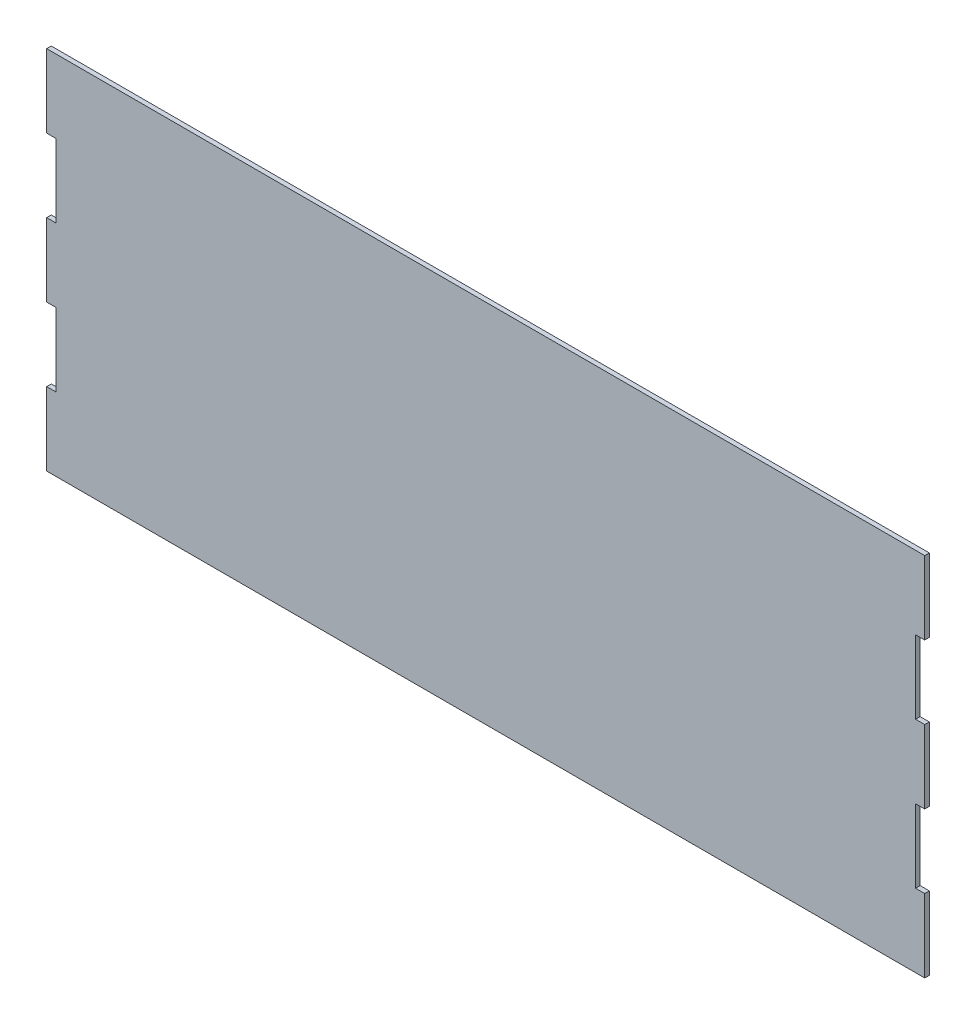
SolidWorks part; units mm, degrees
ref_plane "Front Plane" through (0, 0, 0) normal (0, 0, 1) x (1, 0, 0)
ref_plane "Top Plane" through (0, 0, 0) normal (0, 1, 0) x (1, 0, 0)
ref_plane "Right Plane" through (0, 0, 0) normal (1, 0, 0) x (0, 0, -1)
sketch "Sketch1" plane through (0, 0, 0) normal (0, 0, 1) x (1, 0, 0)
  line L0 (0, 203.2) -> (6.35, 203.2)
  line L1 (0, 0) -> (609.6, 0)
  line L2 (0, 0) -> (0, 50.8)
  line L3 (0, 254) -> (609.6, 254)
  line L4 (609.6, 0) -> (609.6, 50.8)
  line L5 (6.35, 203.2) -> (6.35, 152.4)
  line L6 (6.35, 152.4) -> (0, 152.4)
  line L7 (0, 101.6) -> (6.35, 101.6)
  line L8 (6.35, 101.6) -> (6.35, 50.8)
  line L9 (6.35, 50.8) -> (0, 50.8)
  line L10 (0, 0) -> (6.35, 0)
  line L11 (6.35, 0) -> (6.35, -50.8)
  line L12 (6.35, -50.8) -> (0, -50.8)
  line L13 (0, 101.6) -> (0, 152.4)
  line L14 (0, 203.2) -> (0, 254)
  line L15 (304.8, 254) -> (304.8, 0) construction
  line L16 (603.25, 50.8) -> (609.6, 50.8)
  line L17 (603.25, 101.6) -> (603.25, 50.8)
  line L18 (609.6, 101.6) -> (603.25, 101.6)
  line L19 (603.25, 152.4) -> (609.6, 152.4)
  line L20 (603.25, 203.2) -> (603.25, 152.4)
  line L21 (609.6, 203.2) -> (603.25, 203.2)
  line L22 (609.6, 203.2) -> (609.6, 254)
  line L23 (609.6, 101.6) -> (609.6, 152.4)
  line L24 (25.4, 254) -> (25.4, 0) construction
  line L25 (584.2, 254) -> (584.2, 0) construction
  dimension "D1" = 254
  dimension "D2" = 609.6
  dimension "D3" = 6.35
  dimension "D4" = 50.8
  dimension "D5" = 50.8
  dimension "D7" = 25.4
  dimension "D8" = 25.4
  dimension "D6" = 3
extrude "Boss-Extrude1" add sketch "Sketch1" along normal blind 3.175 contours L18 L23 L19 L20 L21 L22 L3 L14 L0 L5 L6 L13 L7 L8 L9 L2 L1 L4 L16 L17 region at (304.8, 127, 0)
sketch "Sketch4" plane through (0, 0, 3.175) normal (0, 0, 1) x (1, 0, 0)
  line L0 (327.574, 254) -> (327.574, 0) construction
  line L1 (331.2055, -0.0167) -> (331.2055, 59.8139)
  line L2 (331.2055, 74.3399) -> (331.2055, 179.5864)
  line L3 (331.2055, 194.1124) -> (331.2055, 254)
  line L4 (327.574, 134.2248) -> (327.574, 239.474)
  line L5 (327.574, 14.4495) -> (327.574, 119.6988)
  line L6 (584.2, 194.1124) -> (584.2, 254)
  line L7 (84.2635, -0.0167) -> (77.0005, -0.0167)
  line L8 (331.2055, -0.0167) -> (338.4685, -0.0167)
  line L9 (331.2055, 254) -> (338.4685, 254)
  line L10 (77.0005, -0.0167) -> (64.8955, -0.0167)
  line L11 (84.2635, 254) -> (77.0005, 254)
  line L12 (77.0005, 254) -> (64.8955, 254)
  line L13 (87.895, 134.2248) -> (87.895, 239.474)
  line L14 (73.369, 134.2248) -> (73.369, 239.474)
  line L15 (80.632, 134.2248) -> (80.632, 239.474)
  line L16 (77.0005, 74.3399) -> (77.0005, 179.5864)
  line L17 (80.632, 14.4495) -> (80.632, 119.6988)
  line L18 (84.2635, 194.1124) -> (84.2635, 254)
  line L19 (87.895, 14.4495) -> (87.895, 119.6988)
  line L20 (77.0005, 194.1124) -> (77.0005, 254)
  line L21 (73.369, 14.4495) -> (73.369, 119.6988)
  line L22 (84.2635, 74.3399) -> (84.2635, 179.5864)
  line L23 (84.2635, -0.0167) -> (84.2635, 59.8139)
  line L24 (77.0005, -0.0167) -> (77.0005, 59.8139)
  line L25 (91.5265, -0.0167) -> (84.2635, -0.0167)
  line L26 (98.7895, 254) -> (91.5265, 254)
  line L27 (91.5265, 254) -> (84.2635, 254)
  line L28 (98.7895, -0.0167) -> (91.5265, -0.0167)
  line L29 (113.3155, 254) -> (106.0525, 254)
  line L30 (106.0525, 254) -> (98.7895, 254)
  line L31 (113.3155, -0.0167) -> (106.0525, -0.0167)
  line L32 (106.0525, -0.0167) -> (98.7895, -0.0167)
  line L33 (95.158, 134.2248) -> (95.158, 239.474)
  line L34 (109.684, 14.4495) -> (109.684, 119.6988)
  line L35 (113.3155, 194.1124) -> (113.3155, 254)
  line L36 (116.947, 134.2248) -> (116.947, 239.474)
  line L37 (91.5265, -0.0167) -> (91.5265, 59.8139)
  line L38 (98.7895, 194.1124) -> (98.7895, 254)
  line L39 (91.5265, 74.3399) -> (91.5265, 179.5864)
  line L40 (109.684, 134.2248) -> (109.684, 239.474)
  line L41 (113.3155, 74.3399) -> (113.3155, 179.5864)
  line L42 (98.7895, 74.3399) -> (98.7895, 179.5864)
  line L43 (106.0525, 74.3399) -> (106.0525, 179.5864)
  line L44 (116.947, 14.4495) -> (116.947, 119.6988)
  line L45 (102.421, 134.2248) -> (102.421, 239.474)
  line L46 (91.5265, 194.1124) -> (91.5265, 254)
  line L47 (95.158, 14.4495) -> (95.158, 119.6988)
  line L48 (98.7895, -0.0167) -> (98.7895, 59.8139)
  line L49 (102.421, 14.4495) -> (102.421, 119.6988)
  line L50 (106.0525, 194.1124) -> (106.0525, 254)
  line L51 (113.3155, -0.0167) -> (113.3155, 59.8139)
  line L52 (106.0525, -0.0167) -> (106.0525, 59.8139)
  line L53 (120.5785, 254) -> (113.3155, 254)
  line L54 (127.8415, -0.0167) -> (120.5785, -0.0167)
  line L55 (120.5785, -0.0167) -> (113.3155, -0.0167)
  line L56 (127.8415, 254) -> (120.5785, 254)
  line L57 (142.3675, -0.0167) -> (135.1045, -0.0167)
  line L58 (135.1045, -0.0167) -> (127.8415, -0.0167)
  line L59 (142.3675, 254) -> (135.1045, 254)
  line L60 (135.1045, 254) -> (127.8415, 254)
  line L61 (138.736, 134.2248) -> (138.736, 239.474)
  line L62 (120.5785, -0.0167) -> (120.5785, 59.8139)
  line L63 (120.5785, 194.1124) -> (120.5785, 254)
  line L64 (127.8415, -0.0167) -> (127.8415, 59.8139)
  line L65 (124.21, 14.4495) -> (124.21, 119.6988)
  line L66 (127.8415, 194.1124) -> (127.8415, 254)
  line L67 (142.3675, 194.1124) -> (142.3675, 254)
  line L68 (120.5785, 74.3399) -> (120.5785, 179.5864)
  line L69 (142.3675, 74.3399) -> (142.3675, 179.5864)
  line L70 (145.999, 14.4495) -> (145.999, 119.6988)
  line L71 (127.8415, 74.3399) -> (127.8415, 179.5864)
  line L72 (145.999, 134.2248) -> (145.999, 239.474)
  line L73 (131.473, 134.2248) -> (131.473, 239.474)
  line L74 (131.473, 14.4495) -> (131.473, 119.6988)
  line L75 (135.1045, 74.3399) -> (135.1045, 179.5864)
  line L76 (135.1045, 194.1124) -> (135.1045, 254)
  line L77 (124.21, 134.2248) -> (124.21, 239.474)
  line L78 (138.736, 14.4495) -> (138.736, 119.6988)
  line L80 (142.3675, -0.0167) -> (142.3675, 59.8139)
  line L81 (135.1045, -0.0167) -> (135.1045, 59.8139)
  line L83 (149.6305, -0.0167) -> (142.3675, -0.0167)
  line L85 (156.8935, -0.0167) -> (149.6305, -0.0167)
  line L86 (156.8935, 254) -> (149.6305, 254)
  line L87 (149.6305, 254) -> (142.3675, 254)
  line L88 (171.4195, -0.0167) -> (164.1565, -0.0167)
  line L89 (164.1565, -0.0167) -> (156.8935, -0.0167)
  line L90 (171.4195, 254) -> (164.1565, 254)
  line L91 (164.1565, 254) -> (156.8935, 254)
  line L92 (175.051, 134.2248) -> (175.051, 239.474)
  line L93 (156.8935, 194.1124) -> (156.8935, 254)
  line L94 (153.262, 134.2248) -> (153.262, 239.474)
  line L95 (149.6305, 194.1124) -> (149.6305, 254)
  line L96 (149.6305, -0.0167) -> (149.6305, 59.8139)
  line L97 (156.8935, 74.3399) -> (156.8935, 179.5864)
  line L98 (149.6305, 74.3399) -> (149.6305, 179.5864)
  line L99 (175.051, 14.4495) -> (175.051, 119.6988)
  line L100 (167.788, 134.2248) -> (167.788, 239.474)
  line L101 (160.525, 134.2248) -> (160.525, 239.474)
  line L102 (171.4195, 74.3399) -> (171.4195, 179.5864)
  line L103 (171.4195, 194.1124) -> (171.4195, 254)
  line L104 (167.788, 14.4495) -> (167.788, 119.6988)
  line L105 (156.8935, -0.0167) -> (156.8935, 59.8139)
  line L106 (164.1565, 74.3399) -> (164.1565, 179.5864)
  line L107 (164.1565, 194.1124) -> (164.1565, 254)
  line L108 (153.262, 14.4495) -> (153.262, 119.6988)
  line L109 (160.525, 14.4495) -> (160.525, 119.6988)
  line L110 (171.4195, -0.0167) -> (171.4195, 59.8139)
  line L111 (164.1565, -0.0167) -> (164.1565, 59.8139)
  line L112 (178.6825, -0.0167) -> (171.4195, -0.0167)
  line L113 (193.2085, 254) -> (185.9455, 254)
  line L114 (185.9455, -0.0167) -> (178.6825, -0.0167)
  line L115 (200.4715, 254) -> (193.2085, 254)
  line L116 (185.9455, 254) -> (178.6825, 254)
  line L117 (178.6825, 254) -> (171.4195, 254)
  line L118 (200.4715, -0.0167) -> (193.2085, -0.0167)
  line L119 (193.2085, -0.0167) -> (185.9455, -0.0167)
  line L120 (182.314, 14.4495) -> (182.314, 119.6988)
  line L121 (185.9455, 74.3399) -> (185.9455, 179.5864)
  line L122 (189.577, 14.4495) -> (189.577, 119.6988)
  line L123 (178.6825, 74.3399) -> (178.6825, 179.5864)
  line L124 (204.103, 134.2248) -> (204.103, 239.474)
  line L125 (193.2085, 194.1124) -> (193.2085, 254)
  line L126 (193.2085, 74.3399) -> (193.2085, 179.5864)
  line L127 (204.103, 14.4495) -> (204.103, 119.6988)
  line L128 (196.84, 134.2248) -> (196.84, 239.474)
  line L129 (189.577, 134.2248) -> (189.577, 239.474)
  line L130 (200.4715, 194.1124) -> (200.4715, 254)
  line L131 (178.6825, -0.0167) -> (178.6825, 59.8139)
  line L132 (185.9455, 194.1124) -> (185.9455, 254)
  line L133 (200.4715, 74.3399) -> (200.4715, 179.5864)
  line L134 (196.84, 14.4495) -> (196.84, 119.6988)
  line L135 (178.6825, 194.1124) -> (178.6825, 254)
  line L136 (182.314, 134.2248) -> (182.314, 239.474)
  line L137 (185.9455, -0.0167) -> (185.9455, 59.8139)
  line L138 (200.4715, -0.0167) -> (200.4715, 59.8139)
  line L139 (193.2085, -0.0167) -> (193.2085, 59.8139)
  line L140 (207.7345, 254) -> (200.4715, 254)
  line L141 (222.2605, 254) -> (214.9975, 254)
  line L142 (214.9975, 254) -> (207.7345, 254)
  line L143 (214.9975, -0.0167) -> (207.7345, -0.0167)
  line L144 (207.7345, -0.0167) -> (200.4715, -0.0167)
  line L145 (229.5235, 254) -> (222.2605, 254)
  line L146 (229.5235, -0.0167) -> (222.2605, -0.0167)
  line L147 (222.2605, -0.0167) -> (214.9975, -0.0167)
  line L148 (214.9975, -0.0167) -> (214.9975, 59.8139)
  line L149 (229.5235, 74.3399) -> (229.5235, 179.5864)
  line L150 (214.9975, 74.3399) -> (214.9975, 179.5864)
  line L151 (222.2605, 194.1124) -> (222.2605, 254)
  line L152 (218.629, 134.2248) -> (218.629, 239.474)
  line L153 (222.2605, 74.3399) -> (222.2605, 179.5864)
  line L154 (211.366, 134.2248) -> (211.366, 239.474)
  line L155 (207.7345, -0.0167) -> (207.7345, 59.8139)
  line L156 (218.629, 14.4495) -> (218.629, 119.6988)
  line L157 (225.892, 14.4495) -> (225.892, 119.6988)
  line L158 (207.7345, 194.1124) -> (207.7345, 254)
  line L159 (233.155, 14.4495) -> (233.155, 119.6988)
  line L160 (214.9975, 194.1124) -> (214.9975, 254)
  line L161 (207.7345, 74.3399) -> (207.7345, 179.5864)
  line L162 (211.366, 14.4495) -> (211.366, 119.6988)
  line L163 (229.5235, 194.1124) -> (229.5235, 254)
  line L164 (233.155, 134.2248) -> (233.155, 239.474)
  line L165 (225.892, 134.2248) -> (225.892, 239.474)
  line L166 (229.5235, -0.0167) -> (229.5235, 59.8139)
  line L167 (222.2605, -0.0167) -> (222.2605, 59.8139)
  line L168 (244.0495, 254) -> (236.7865, 254)
  line L169 (236.7865, 254) -> (229.5235, 254)
  line L170 (244.0495, -0.0167) -> (236.7865, -0.0167)
  line L171 (236.7865, -0.0167) -> (229.5235, -0.0167)
  line L172 (251.3125, 254) -> (244.0495, 254)
  line L173 (258.5755, -0.0167) -> (251.3125, -0.0167)
  line L174 (251.3125, -0.0167) -> (244.0495, -0.0167)
  line L175 (258.5755, 254) -> (251.3125, 254)
  line L176 (244.0495, 194.1124) -> (244.0495, 254)
  line L177 (236.7865, 194.1124) -> (236.7865, 254)
  line L178 (236.7865, 74.3399) -> (236.7865, 179.5864)
  line L179 (247.681, 134.2248) -> (247.681, 239.474)
  line L180 (254.944, 134.2248) -> (254.944, 239.474)
  line L181 (258.5755, 74.3399) -> (258.5755, 179.5864)
  line L182 (244.0495, 74.3399) -> (244.0495, 179.5864)
  line L183 (251.3125, 194.1124) -> (251.3125, 254)
  line L184 (262.207, 134.2248) -> (262.207, 239.474)
  line L185 (244.0495, -0.0167) -> (244.0495, 59.8139)
  line L186 (258.5755, 194.1124) -> (258.5755, 254)
  line L187 (247.681, 14.4495) -> (247.681, 119.6988)
  line L188 (240.418, 134.2248) -> (240.418, 239.474)
  line L189 (254.944, 14.4495) -> (254.944, 119.6988)
  line L190 (262.207, 14.4495) -> (262.207, 119.6988)
  line L191 (251.3125, 74.3399) -> (251.3125, 179.5864)
  line L192 (236.7865, -0.0167) -> (236.7865, 59.8139)
  line L193 (240.418, 14.4495) -> (240.418, 119.6988)
  line L194 (258.5755, -0.0167) -> (258.5755, 59.8139)
  line L195 (251.3125, -0.0167) -> (251.3125, 59.8139)
  line L196 (280.3645, 254) -> (273.1015, 254)
  line L197 (273.1015, -0.0167) -> (265.8385, -0.0167)
  line L198 (265.8385, -0.0167) -> (258.5755, -0.0167)
  line L199 (287.6275, 254) -> (280.3645, 254)
  line L200 (273.1015, 254) -> (265.8385, 254)
  line L201 (265.8385, 254) -> (258.5755, 254)
  line L202 (287.6275, -0.0167) -> (280.3645, -0.0167)
  line L203 (280.3645, -0.0167) -> (273.1015, -0.0167)
  line L204 (283.996, 134.2248) -> (283.996, 239.474)
  line L205 (291.259, 134.2248) -> (291.259, 239.474)
  line L206 (280.3645, 194.1124) -> (280.3645, 254)
  line L207 (269.47, 134.2248) -> (269.47, 239.474)
  line L208 (273.1015, 74.3399) -> (273.1015, 179.5864)
  line L209 (276.733, 134.2248) -> (276.733, 239.474)
  line L210 (287.6275, 74.3399) -> (287.6275, 179.5864)
  line L211 (291.259, 14.4495) -> (291.259, 119.6988)
  line L212 (287.6275, 194.1124) -> (287.6275, 254)
  line L213 (276.733, 14.4495) -> (276.733, 119.6988)
  line L214 (273.1015, 194.1124) -> (273.1015, 254)
  line L215 (269.47, 14.4495) -> (269.47, 119.6988)
  line L216 (273.1015, -0.0167) -> (273.1015, 59.8139)
  line L217 (265.8385, -0.0167) -> (265.8385, 59.8139)
  line L218 (283.996, 14.4495) -> (283.996, 119.6988)
  line L219 (280.3645, 74.3399) -> (280.3645, 179.5864)
  line L220 (265.8385, 74.3399) -> (265.8385, 179.5864)
  line L221 (265.8385, 194.1124) -> (265.8385, 254)
  line L222 (287.6275, -0.0167) -> (287.6275, 59.8139)
  line L223 (280.3645, -0.0167) -> (280.3645, 59.8139)
  line L224 (294.8905, 254) -> (287.6275, 254)
  line L225 (294.8905, -0.0167) -> (287.6275, -0.0167)
  line L226 (298.522, 14.4495) -> (298.522, 119.6988)
  line L227 (294.8905, 74.3399) -> (294.8905, 179.5864)
  line L228 (294.8905, -0.0167) -> (294.8905, 59.8139)
  line L229 (294.8905, 194.1124) -> (294.8905, 254)
  line L230 (298.522, 134.2248) -> (298.522, 239.474)
  line L231 (302.1535, 254) -> (294.8905, 254)
  line L232 (302.1535, -0.0167) -> (294.8905, -0.0167)
  line L233 (302.1535, -0.0167) -> (302.1535, 59.8139)
  line L234 (302.1535, 194.1124) -> (302.1535, 254)
  line L235 (305.785, 14.4495) -> (305.785, 119.6988)
  line L236 (302.1535, 74.3399) -> (302.1535, 179.5864)
  line L237 (305.785, 134.2248) -> (305.785, 239.474)
  line L238 (309.4165, 254) -> (302.1535, 254)
  line L239 (309.4165, -0.0167) -> (302.1535, -0.0167)
  line L240 (313.048, 14.4495) -> (313.048, 119.6988)
  line L241 (309.4165, 74.3399) -> (309.4165, 179.5864)
  line L242 (313.048, 134.2248) -> (313.048, 239.474)
  line L243 (309.4165, 194.1124) -> (309.4165, 254)
  line L244 (309.4165, -0.0167) -> (309.4165, 59.8139)
  line L245 (316.6795, 254) -> (309.4165, 254)
  line L246 (316.6795, -0.0167) -> (309.4165, -0.0167)
  line L247 (320.311, 14.4495) -> (320.311, 119.6988)
  line L248 (320.311, 134.2248) -> (320.311, 239.474)
  line L249 (316.6795, 194.1124) -> (316.6795, 254)
  line L250 (316.6795, 74.3399) -> (316.6795, 179.5864)
  line L251 (316.6795, -0.0167) -> (316.6795, 59.8139)
  line L252 (70.948, -0.0167) -> (70.948, 59.8139)
  line L253 (70.948, 74.3399) -> (70.948, 179.5864)
  line L254 (323.9425, 254) -> (316.6795, 254)
  line L255 (323.9425, -0.0167) -> (316.6795, -0.0167)
  line L256 (70.948, 194.1124) -> (70.948, 254)
  line L257 (323.9425, 194.1124) -> (323.9425, 254)
  line L258 (323.9425, 74.3399) -> (323.9425, 179.5864)
  line L259 (323.9425, -0.0167) -> (323.9425, 59.8139)
  line L260 (70.948, 260.5884) -> (70.948, -3.5124) construction
  line L261 (25.4, 254) -> (25.4, 0) construction
  line L262 (0, 0) -> (0, 50.8) construction
  line L263 (43.1065, 254) -> (50.3695, 254)
  line L264 (43.1065, -0.0167) -> (50.3695, -0.0167)
  line L265 (35.8435, -0.0167) -> (35.8435, 59.8139)
  line L266 (28.5805, -0.0167) -> (28.5805, 59.8139)
  line L267 (35.8435, 194.1124) -> (35.8435, 254)
  line L268 (39.475, 14.4495) -> (39.475, 119.6988)
  line L269 (43.1065, -0.0167) -> (43.1065, 59.8139)
  line L270 (39.475, 134.2248) -> (39.475, 239.474)
  line L271 (24.949, 14.4495) -> (24.949, 119.6988)
  line L272 (35.8435, 74.3399) -> (35.8435, 179.5864)
  line L273 (43.1065, 74.3399) -> (43.1065, 179.5864)
  line L274 (28.5805, 74.3399) -> (28.5805, 179.5864)
  line L275 (32.212, 134.2248) -> (32.212, 239.474)
  line L276 (43.1065, 194.1124) -> (43.1065, 254)
  line L277 (24.949, 134.2248) -> (24.949, 239.474)
  line L278 (28.5805, 194.1124) -> (28.5805, 254)
  line L279 (32.212, 14.4495) -> (32.212, 119.6988)
  line L280 (35.8435, -0.0167) -> (43.1065, -0.0167)
  line L281 (28.5805, -0.0167) -> (35.8435, -0.0167)
  line L282 (35.8435, 254) -> (43.1065, 254)
  line L283 (28.5805, 254) -> (35.8435, 254)
  line L284 (46.738, 14.4495) -> (46.738, 119.6988)
  line L285 (50.3695, 194.1124) -> (50.3695, 254)
  line L286 (50.3695, 74.3399) -> (50.3695, 179.5864)
  line L287 (50.3695, -0.0167) -> (50.3695, 59.8139)
  line L288 (46.738, 134.2248) -> (46.738, 239.474)
  line L289 (50.3695, 254) -> (57.6325, 254)
  line L290 (50.3695, -0.0167) -> (57.6325, -0.0167)
  line L291 (64.8955, -0.0167) -> (64.8955, 59.8139)
  line L292 (57.6325, -0.0167) -> (57.6325, 59.8139)
  line L293 (57.6325, 74.3399) -> (57.6325, 179.5864)
  line L294 (68.527, 14.4495) -> (68.527, 119.6988)
  line L295 (64.8955, 194.1124) -> (64.8955, 254)
  line L296 (54.001, 14.4495) -> (54.001, 119.6988)
  line L297 (57.6325, 194.1124) -> (57.6325, 254)
  line L298 (61.264, 14.4495) -> (61.264, 119.6988)
  line L299 (64.8955, 74.3399) -> (64.8955, 179.5864)
  line L300 (61.264, 134.2248) -> (61.264, 239.474)
  line L301 (68.527, 134.2248) -> (68.527, 239.474)
  line L302 (54.001, 134.2248) -> (54.001, 239.474)
  line L303 (57.6325, 254) -> (64.8955, 254)
  line L304 (57.6325, -0.0167) -> (64.8955, -0.0167)
  line L541 (584.2, 74.3399) -> (584.2, 179.5864)
  line L542 (584.2, -0.0167) -> (584.2, 59.8139)
  line L543 (338.4685, -0.0167) -> (338.4685, 59.8139)
  line L544 (338.4685, 74.3399) -> (338.4685, 179.5864)
  line L545 (338.4685, 194.1124) -> (338.4685, 254)
  line L546 (334.837, 134.2248) -> (334.837, 239.474)
  line L547 (334.837, 14.4495) -> (334.837, 119.6988)
  line L548 (338.4685, -0.0167) -> (345.7315, -0.0167)
  line L549 (338.4685, 254) -> (345.7315, 254)
  line L550 (345.7315, -0.0167) -> (345.7315, 59.8139)
  line L551 (345.7315, 194.1124) -> (345.7315, 254)
  line L552 (342.1, 134.2248) -> (342.1, 239.474)
  line L553 (345.7315, 74.3399) -> (345.7315, 179.5864)
  line L554 (342.1, 14.4495) -> (342.1, 119.6988)
  line L555 (345.7315, -0.0167) -> (352.9945, -0.0167)
  line L556 (345.7315, 254) -> (352.9945, 254)
  line L557 (349.363, 134.2248) -> (349.363, 239.474)
  line L558 (352.9945, 74.3399) -> (352.9945, 179.5864)
  line L559 (349.363, 14.4495) -> (349.363, 119.6988)
  line L560 (352.9945, 194.1124) -> (352.9945, 254)
  line L561 (352.9945, -0.0167) -> (352.9945, 59.8139)
  line L562 (352.9945, -0.0167) -> (360.2575, -0.0167)
  line L563 (352.9945, 254) -> (360.2575, 254)
  line L564 (356.626, 134.2248) -> (356.626, 239.474)
  line L565 (360.2575, 194.1124) -> (360.2575, 254)
  line L566 (360.2575, -0.0167) -> (360.2575, 59.8139)
  line L567 (360.2575, 74.3399) -> (360.2575, 179.5864)
  line L568 (356.626, 14.4495) -> (356.626, 119.6988)
  line L569 (360.2575, -0.0167) -> (367.5205, -0.0167)
  line L570 (360.2575, 254) -> (367.5205, 254)
  line L571 (374.7835, -0.0167) -> (374.7835, 59.8139)
  line L572 (367.5205, -0.0167) -> (367.5205, 59.8139)
  line L573 (389.3095, 194.1124) -> (389.3095, 254)
  line L574 (389.3095, 74.3399) -> (389.3095, 179.5864)
  line L575 (374.7835, 74.3399) -> (374.7835, 179.5864)
  line L576 (371.152, 14.4495) -> (371.152, 119.6988)
  line L577 (389.3095, -0.0167) -> (389.3095, 59.8139)
  line L578 (382.0465, -0.0167) -> (382.0465, 59.8139)
  line L579 (385.678, 14.4495) -> (385.678, 119.6988)
  line L580 (382.0465, 194.1124) -> (382.0465, 254)
  line L581 (378.415, 14.4495) -> (378.415, 119.6988)
  line L582 (367.5205, 194.1124) -> (367.5205, 254)
  line L583 (363.889, 14.4495) -> (363.889, 119.6988)
  line L584 (367.5205, 74.3399) -> (367.5205, 179.5864)
  line L585 (378.415, 134.2248) -> (378.415, 239.474)
  line L586 (382.0465, 74.3399) -> (382.0465, 179.5864)
  line L587 (385.678, 134.2248) -> (385.678, 239.474)
  line L588 (374.7835, 194.1124) -> (374.7835, 254)
  line L589 (363.889, 134.2248) -> (363.889, 239.474)
  line L590 (371.152, 134.2248) -> (371.152, 239.474)
  line L591 (374.7835, -0.0167) -> (382.0465, -0.0167)
  line L592 (367.5205, -0.0167) -> (374.7835, -0.0167)
  line L593 (389.3095, 254) -> (396.5725, 254)
  line L594 (382.0465, 254) -> (389.3095, 254)
  line L595 (367.5205, 254) -> (374.7835, 254)
  line L596 (389.3095, -0.0167) -> (396.5725, -0.0167)
  line L597 (382.0465, -0.0167) -> (389.3095, -0.0167)
  line L598 (374.7835, 254) -> (382.0465, 254)
  line L599 (403.8355, -0.0167) -> (403.8355, 59.8139)
  line L600 (396.5725, -0.0167) -> (396.5725, 59.8139)
  line L601 (414.73, 14.4495) -> (414.73, 119.6988)
  line L602 (418.3615, -0.0167) -> (418.3615, 59.8139)
  line L603 (403.8355, 74.3399) -> (403.8355, 179.5864)
  line L604 (392.941, 14.4495) -> (392.941, 119.6988)
  line L605 (400.204, 14.4495) -> (400.204, 119.6988)
  line L606 (414.73, 134.2248) -> (414.73, 239.474)
  line L607 (407.467, 14.4495) -> (407.467, 119.6988)
  line L608 (396.5725, 194.1124) -> (396.5725, 254)
  line L609 (411.0985, -0.0167) -> (411.0985, 59.8139)
  line L610 (392.941, 134.2248) -> (392.941, 239.474)
  line L611 (403.8355, 194.1124) -> (403.8355, 254)
  line L612 (411.0985, 74.3399) -> (411.0985, 179.5864)
  line L613 (396.5725, 74.3399) -> (396.5725, 179.5864)
  line L614 (400.204, 134.2248) -> (400.204, 239.474)
  line L615 (407.467, 134.2248) -> (407.467, 239.474)
  line L616 (418.3615, 74.3399) -> (418.3615, 179.5864)
  line L617 (418.3615, 194.1124) -> (418.3615, 254)
  line L618 (411.0985, 194.1124) -> (411.0985, 254)
  line L619 (396.5725, 254) -> (403.8355, 254)
  line L620 (403.8355, -0.0167) -> (411.0985, -0.0167)
  line L621 (396.5725, -0.0167) -> (403.8355, -0.0167)
  line L622 (403.8355, 254) -> (411.0985, 254)
  line L623 (418.3615, -0.0167) -> (425.6245, -0.0167)
  line L624 (411.0985, -0.0167) -> (418.3615, -0.0167)
  line L625 (418.3615, 254) -> (425.6245, 254)
  line L626 (411.0985, 254) -> (418.3615, 254)
  line L627 (432.8875, -0.0167) -> (432.8875, 59.8139)
  line L628 (425.6245, -0.0167) -> (425.6245, 59.8139)
  line L629 (429.256, 134.2248) -> (429.256, 239.474)
  line L630 (421.993, 134.2248) -> (421.993, 239.474)
  line L631 (425.6245, 194.1124) -> (425.6245, 254)
  line L632 (443.782, 14.4495) -> (443.782, 119.6988)
  line L633 (447.4135, 74.3399) -> (447.4135, 179.5864)
  line L634 (440.1505, 194.1124) -> (440.1505, 254)
  line L635 (421.993, 14.4495) -> (421.993, 119.6988)
  line L636 (447.4135, 194.1124) -> (447.4135, 254)
  line L637 (429.256, 14.4495) -> (429.256, 119.6988)
  line L638 (436.519, 14.4495) -> (436.519, 119.6988)
  line L639 (447.4135, -0.0167) -> (447.4135, 59.8139)
  line L640 (443.782, 134.2248) -> (443.782, 239.474)
  line L641 (432.8875, 74.3399) -> (432.8875, 179.5864)
  line L642 (436.519, 134.2248) -> (436.519, 239.474)
  line L643 (432.8875, 194.1124) -> (432.8875, 254)
  line L644 (440.1505, 74.3399) -> (440.1505, 179.5864)
  line L645 (425.6245, 74.3399) -> (425.6245, 179.5864)
  line L646 (440.1505, -0.0167) -> (440.1505, 59.8139)
  line L647 (432.8875, -0.0167) -> (440.1505, -0.0167)
  line L648 (425.6245, -0.0167) -> (432.8875, -0.0167)
  line L649 (425.6245, 254) -> (432.8875, 254)
  line L650 (447.4135, -0.0167) -> (454.6765, -0.0167)
  line L651 (440.1505, -0.0167) -> (447.4135, -0.0167)
  line L652 (440.1505, 254) -> (447.4135, 254)
  line L653 (432.8875, 254) -> (440.1505, 254)
  line L654 (447.4135, 254) -> (454.6765, 254)
  line L655 (461.9395, -0.0167) -> (461.9395, 59.8139)
  line L656 (454.6765, -0.0167) -> (454.6765, 59.8139)
  line L657 (469.2025, -0.0167) -> (469.2025, 59.8139)
  line L658 (472.834, 134.2248) -> (472.834, 239.474)
  line L659 (476.4655, 194.1124) -> (476.4655, 254)
  line L660 (458.308, 14.4495) -> (458.308, 119.6988)
  line L661 (454.6765, 74.3399) -> (454.6765, 179.5864)
  line L662 (469.2025, 194.1124) -> (469.2025, 254)
  line L663 (476.4655, -0.0167) -> (476.4655, 59.8139)
  line L664 (454.6765, 194.1124) -> (454.6765, 254)
  line L665 (465.571, 134.2248) -> (465.571, 239.474)
  line L666 (458.308, 134.2248) -> (458.308, 239.474)
  line L667 (451.045, 14.4495) -> (451.045, 119.6988)
  line L668 (461.9395, 74.3399) -> (461.9395, 179.5864)
  line L669 (461.9395, 194.1124) -> (461.9395, 254)
  line L670 (451.045, 134.2248) -> (451.045, 239.474)
  line L671 (476.4655, 74.3399) -> (476.4655, 179.5864)
  line L672 (465.571, 14.4495) -> (465.571, 119.6988)
  line L673 (469.2025, 74.3399) -> (469.2025, 179.5864)
  line L674 (472.834, 14.4495) -> (472.834, 119.6988)
  line L675 (461.9395, -0.0167) -> (469.2025, -0.0167)
  line L676 (454.6765, -0.0167) -> (461.9395, -0.0167)
  line L677 (476.4655, 254) -> (483.7285, 254)
  line L678 (469.2025, 254) -> (476.4655, 254)
  line L679 (454.6765, 254) -> (461.9395, 254)
  line L680 (469.2025, -0.0167) -> (476.4655, -0.0167)
  line L681 (461.9395, 254) -> (469.2025, 254)
  line L682 (476.4655, -0.0167) -> (483.7285, -0.0167)
  line L683 (490.9915, -0.0167) -> (490.9915, 59.8139)
  line L684 (483.7285, -0.0167) -> (483.7285, 59.8139)
  line L685 (494.623, 14.4495) -> (494.623, 119.6988)
  line L686 (501.886, 14.4495) -> (501.886, 119.6988)
  line L687 (490.9915, 194.1124) -> (490.9915, 254)
  line L688 (490.9915, 74.3399) -> (490.9915, 179.5864)
  line L689 (498.2545, -0.0167) -> (498.2545, 59.8139)
  line L690 (487.36, 14.4495) -> (487.36, 119.6988)
  line L691 (483.7285, 194.1124) -> (483.7285, 254)
  line L692 (483.7285, 74.3399) -> (483.7285, 179.5864)
  line L693 (494.623, 134.2248) -> (494.623, 239.474)
  line L694 (487.36, 134.2248) -> (487.36, 239.474)
  line L695 (480.097, 14.4495) -> (480.097, 119.6988)
  line L696 (505.5175, 74.3399) -> (505.5175, 179.5864)
  line L697 (498.2545, 74.3399) -> (498.2545, 179.5864)
  line L698 (505.5175, -0.0167) -> (505.5175, 59.8139)
  line L699 (505.5175, 194.1124) -> (505.5175, 254)
  line L700 (501.886, 134.2248) -> (501.886, 239.474)
  line L701 (498.2545, 194.1124) -> (498.2545, 254)
  line L702 (480.097, 134.2248) -> (480.097, 239.474)
  line L703 (490.9915, 254) -> (498.2545, 254)
  line L704 (483.7285, 254) -> (490.9915, 254)
  line L705 (490.9915, -0.0167) -> (498.2545, -0.0167)
  line L706 (483.7285, -0.0167) -> (490.9915, -0.0167)
  line L707 (505.5175, 254) -> (512.7805, 254)
  line L708 (498.2545, 254) -> (505.5175, 254)
  line L709 (498.2545, -0.0167) -> (505.5175, -0.0167)
  line L710 (505.5175, -0.0167) -> (512.7805, -0.0167)
  line L711 (520.0435, -0.0167) -> (520.0435, 59.8139)
  line L712 (512.7805, -0.0167) -> (512.7805, 59.8139)
  line L713 (516.412, 14.4495) -> (516.412, 119.6988)
  line L714 (530.938, 134.2248) -> (530.938, 239.474)
  line L715 (520.0435, 194.1124) -> (520.0435, 254)
  line L716 (520.0435, 74.3399) -> (520.0435, 179.5864)
  line L717 (523.675, 14.4495) -> (523.675, 119.6988)
  line L718 (523.675, 134.2248) -> (523.675, 239.474)
  line L719 (509.149, 134.2248) -> (509.149, 239.474)
  line L720 (527.3065, 74.3399) -> (527.3065, 179.5864)
  line L721 (509.149, 14.4495) -> (509.149, 119.6988)
  line L722 (512.7805, 74.3399) -> (512.7805, 179.5864)
  line L723 (534.5695, 74.3399) -> (534.5695, 179.5864)
  line L724 (512.7805, 194.1124) -> (512.7805, 254)
  line L725 (527.3065, 194.1124) -> (527.3065, 254)
  line L726 (530.938, 14.4495) -> (530.938, 119.6988)
  line L727 (527.3065, -0.0167) -> (527.3065, 59.8139)
  line L728 (534.5695, 194.1124) -> (534.5695, 254)
  line L729 (534.5695, -0.0167) -> (534.5695, 59.8139)
  line L730 (516.412, 134.2248) -> (516.412, 239.474)
  line L731 (520.0435, 254) -> (527.3065, 254)
  line L732 (512.7805, 254) -> (520.0435, 254)
  line L733 (520.0435, -0.0167) -> (527.3065, -0.0167)
  line L734 (512.7805, -0.0167) -> (520.0435, -0.0167)
  line L735 (527.3065, 254) -> (534.5695, 254)
  line L736 (534.5695, -0.0167) -> (541.8325, -0.0167)
  line L737 (527.3065, -0.0167) -> (534.5695, -0.0167)
  line L738 (534.5695, 254) -> (541.8325, 254)
  line L739 (549.0955, -0.0167) -> (549.0955, 59.8139)
  line L740 (541.8325, -0.0167) -> (541.8325, 59.8139)
  line L741 (549.0955, 194.1124) -> (549.0955, 254)
  line L742 (552.727, 14.4495) -> (552.727, 119.6988)
  line L743 (556.3585, -0.0167) -> (556.3585, 59.8139)
  line L744 (559.99, 14.4495) -> (559.99, 119.6988)
  line L745 (563.6215, 194.1124) -> (563.6215, 254)
  line L746 (552.727, 134.2248) -> (552.727, 239.474)
  line L747 (538.201, 14.4495) -> (538.201, 119.6988)
  line L748 (549.0955, 74.3399) -> (549.0955, 179.5864)
  line L749 (556.3585, 74.3399) -> (556.3585, 179.5864)
  line L750 (541.8325, 74.3399) -> (541.8325, 179.5864)
  line L751 (545.464, 134.2248) -> (545.464, 239.474)
  line L752 (563.6215, 74.3399) -> (563.6215, 179.5864)
  line L753 (556.3585, 194.1124) -> (556.3585, 254)
  line L754 (563.6215, -0.0167) -> (563.6215, 59.8139)
  line L755 (538.201, 134.2248) -> (538.201, 239.474)
  line L756 (541.8325, 194.1124) -> (541.8325, 254)
  line L757 (545.464, 14.4495) -> (545.464, 119.6988)
  line L758 (559.99, 134.2248) -> (559.99, 239.474)
  line L759 (549.0955, -0.0167) -> (556.3585, -0.0167)
  line L760 (541.8325, -0.0167) -> (549.0955, -0.0167)
  line L761 (549.0955, 254) -> (556.3585, 254)
  line L762 (541.8325, 254) -> (549.0955, 254)
  line L763 (556.3585, -0.0167) -> (563.6215, -0.0167)
  line L764 (563.6215, 254) -> (570.8845, 254)
  line L765 (556.3585, 254) -> (563.6215, 254)
  line L766 (563.6215, -0.0167) -> (570.8845, -0.0167)
  line L767 (578.1475, -0.0167) -> (578.1475, 59.8139)
  line L768 (570.8845, -0.0167) -> (570.8845, 59.8139)
  line L769 (570.8845, 74.3399) -> (570.8845, 179.5864)
  line L770 (581.779, 14.4495) -> (581.779, 119.6988)
  line L771 (578.1475, 194.1124) -> (578.1475, 254)
  line L772 (567.253, 14.4495) -> (567.253, 119.6988)
  line L773 (570.8845, 194.1124) -> (570.8845, 254)
  line L774 (574.516, 14.4495) -> (574.516, 119.6988)
  line L775 (578.1475, 74.3399) -> (578.1475, 179.5864)
  line L776 (574.516, 134.2248) -> (574.516, 239.474)
  line L777 (581.779, 134.2248) -> (581.779, 239.474)
  line L778 (567.253, 134.2248) -> (567.253, 239.474)
  line L779 (578.1475, 254) -> (584.2, 254)
  line L780 (570.8845, 254) -> (578.1475, 254)
  line L781 (578.1475, -0.0167) -> (584.2, -0.0167)
  line L782 (570.8845, -0.0167) -> (578.1475, -0.0167)
  line L783 (584.2, 254) -> (584.2, 0) construction
  line L784 (0, 254) -> (609.6, 254) construction
  line L785 (0, 0) -> (609.6, 0) construction
  line L786 (609.6, 203.2) -> (609.6, 254) construction
  point P0 (405.0694, 126.9618)
  point P1 (405.0694, 126.9642)
  point P2 (405.0718, 126.9642)
  point P378 (250.0762, 126.9642)
  point P379 (250.0786, 126.9642)
  point P380 (250.0786, 126.9618)
  dimension "D1" = 25.4
  dimension "D2" = 25.4
